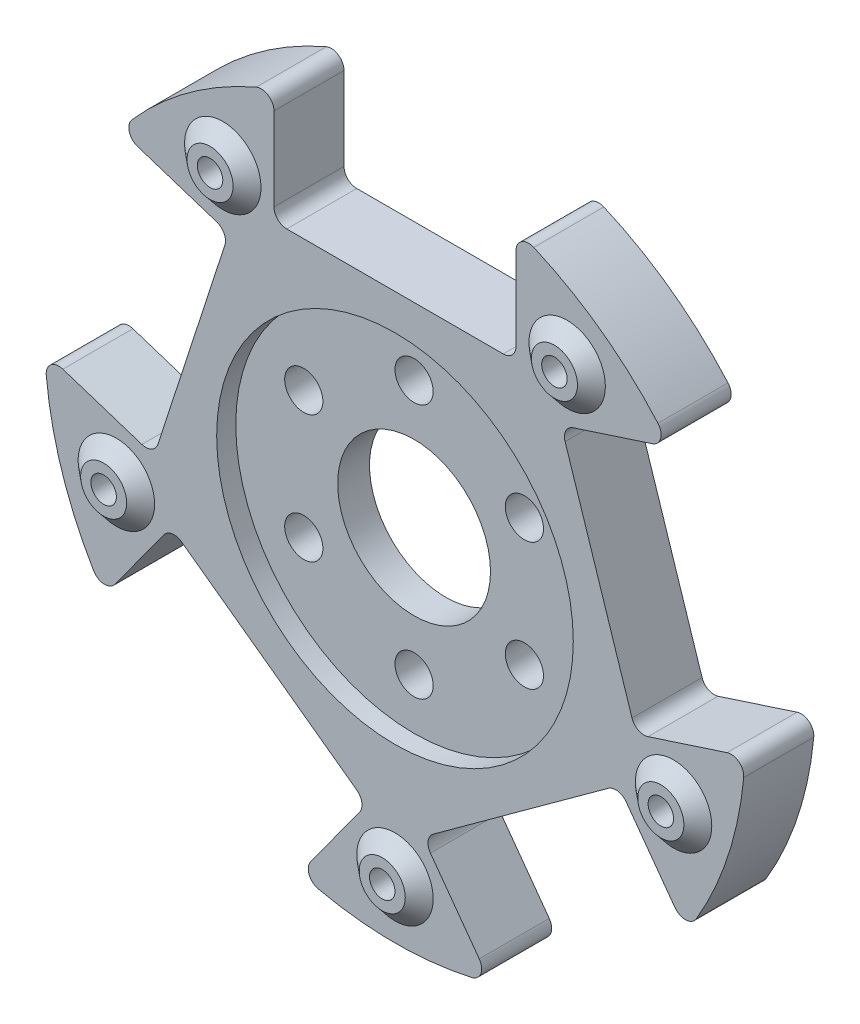
SolidWorks part; units mm, degrees
material "1060 Alloy"
ref_plane "Front Plane" through (0, 0, 0) normal (0, 0, 1) x (1, 0, 0)
ref_plane "Top Plane" through (0, 0, 0) normal (0, 1, 0) x (1, 0, 0)
ref_plane "Right Plane" through (0, 0, 0) normal (1, 0, 0) x (0, 0, -1)
sketch "Sketch2" plane through (0, 0, 0) normal (0, 0, 1) x (1, 0, 0)
  line L0 (-9.5, 25.807) -> (-9.5, 16.807)
  line L1 (-9.5, 16.807) -> (9.5, 16.807)
  line L2 (9.5, 16.807) -> (9.5, 25.807)
  line L3 (0, 0) -> (-50000, 0) construction
  line L4 (0, 0) -> (0, -50000) construction
  line L5 (21.6082, 17.0098) -> (13.0487, 14.2287)
  line L6 (18.92, -3.8414) -> (27.4796, -1.0602)
  line L7 (13.0487, 14.2287) -> (18.92, -3.8414)
  line L8 (22.8546, -15.2943) -> (17.5646, -8.0132)
  line L9 (2.1932, -19.1811) -> (7.4833, -26.4622)
  line L10 (17.5646, -8.0132) -> (2.1932, -19.1811)
  line L11 (-7.4833, -26.4622) -> (-2.1932, -19.1811)
  line L12 (-17.5646, -8.0132) -> (-22.8546, -15.2943)
  line L13 (-2.1932, -19.1811) -> (-17.5646, -8.0132)
  line L14 (-27.4796, -1.0602) -> (-18.92, -3.8414)
  line L15 (-13.0487, 14.2287) -> (-21.6082, 17.0098)
  line L16 (-18.92, -3.8414) -> (-13.0487, 14.2287)
  arc A0 (-9.5, 25.807) -> (-21.6082, 17.0098) centre (0, 0) ccw
  circle A1 centre (0, 0) radius 6
  circle A2 centre (0, 10) radius 1.5
  circle A5 centre (0, 0) radius 14
  arc A6 (21.6082, 17.0098) -> (9.5, 25.807) centre (0, 0) ccw
  arc A7 (22.8546, -15.2943) -> (27.5, 0) centre (0, 0) ccw
  arc A8 (-7.4833, -26.4622) -> (7.4833, -26.4622) centre (0, 0) ccw
  arc A9 (-27.5, 0) -> (-22.8546, -15.2943) centre (0, 0) ccw
  circle A10 centre (8.6603, 5) radius 1.5
  circle A11 centre (8.6603, -5) radius 1.5
  circle A12 centre (0, -10) radius 1.5
  circle A13 centre (-8.6603, -5) radius 1.5
  circle A14 centre (-8.6603, 5) radius 1.5
  point P12 (0, 0)
  point P39 (0, 0)
  point P47 (0, 0)
  dimension "D1" = 55
  dimension "D2" = 12
  dimension "D4" = 3
  dimension "D8" = 28
  dimension "D3" = 10
  dimension "D6" = 19
  dimension "D7" = 9
  dimension "D9" = 5
  dimension "D5" = 6
extrude "Boss-Extrude1" add sketch "Sketch2" along normal mid plane 5.5 contours L14 A9 L12 L13 L11 A8 L9 L10 L8 A7 L6 L7 L5 A6 L2 L1 L0 A0 L15 L16 A5 region at (-10.2656, 21.307, 0)
extrude "Boss-Extrude2" add sketch "Sketch2<3>" along normal mid plane 2.5 contours A5 A1 A2 region at (-13.604, 0, 0)
sketch "Sketch2<3>" plane through (0, 0, 0) normal (0, 0, 1) x (1, 0, 0) same geometry as "Sketch2"
fillet "Fillet1" radius 1 20 edges at (-18.92, -3.8414, 0) (-13.0487, 14.2287, 0) (-17.5646, -8.0132, 0) (-2.1932, -19.1811, 0) (17.5646, -8.0132, 0) (2.1932, -19.1811, 0) (18.92, -3.8414, 0) (13.0487, 14.2287, 0) (9.5, 16.807, 0) (-9.5, 16.807, 0) (-9.5, 25.807, 0) (9.5, 25.807, 0) (21.6082, 17.0098, 0) (27.4796, -1.0602, 0) (22.8546, -15.2943, 0) (7.4833, -26.4622, 0) (-7.4833, -26.4622, 0) (-22.8546, -15.2943, 0) (-27.4796, -1.0602, 0) (-21.6082, 17.0098, 0)
sketch "Sketch3" plane through (0, 0, 2.75) normal (0, 0, 1) x (1, 0, 0)
  line L0 (0, 0) -> (22.2845, 30.672) construction
  line L1 (0, 0) -> (0, 37.4243) construction
  circle A0 centre (13.5191, 18.6074) radius 3
  circle A2 centre (21.8743, -7.1074) radius 3
  circle A3 centre (0, -23) radius 3
  circle A4 centre (-21.8743, -7.1074) radius 3
  circle A5 centre (-13.5191, 18.6074) radius 3
  point P19 (0, 0)
  dimension "D2" = 6
  dimension "D1" = 23
  dimension "D3" = 36
  dimension "D4" = 5
extrude "Boss-Extrude3" add sketch "Sketch3" along normal blind 1 draft 50
sketch "Sketch4" plane through (0, 0, 3.75) normal (0, 0, 1) x (1, 0, 0)
  circle A0 centre (13.5191, 18.6074) radius 1
  circle A1 centre (21.8743, -7.1074) radius 1
  circle A2 centre (0, -23) radius 1
  circle A3 centre (-21.8743, -7.1074) radius 1
  circle A4 centre (-13.5191, 18.6074) radius 1
  point P14 (0, 0)
  dimension "D1" = 2
  dimension "D2" = 5
extrude "Cut-Extrude1" cut sketch "Sketch4" against normal blind 2
sketch "Sketch5" plane through (0, 0, -2.75) normal (0, 0, -1) x (-1, 0, 0)
  line L0 (0, 0) -> (0, -50000) construction
  line L1 (0, 0) -> (29389.2626, 40450.8497) construction
  circle A0 centre (13.5191, 18.6074) radius 3
  circle A1 centre (21.8743, -7.1074) radius 3
  circle A2 centre (0, -23) radius 3
  circle A3 centre (-21.8743, -7.1074) radius 3
  circle A4 centre (-13.5191, 18.6074) radius 3
  point P17 (0, 0)
  dimension "D2" = 6
  dimension "D1" = 23
  dimension "D3" = 36
  dimension "D4" = 5
extrude "Boss-Extrude5" add sketch "Sketch5" along normal blind 1 draft 50
sketch "Sketch6" plane through (0, 0, -3.75) normal (0, 0, -1) x (-1, 0, 0)
  circle A0 centre (13.5191, 18.6074) radius 1
  circle A1 centre (21.8743, -7.1074) radius 1
  circle A2 centre (0, -23) radius 1
  circle A3 centre (-21.8743, -7.1074) radius 1
  circle A4 centre (-13.5191, 18.6074) radius 1
  point P13 (0, 0)
  dimension "D1" = 2
  dimension "D2" = 5
extrude "Cut-Extrude2" cut sketch "Sketch6" against normal blind 1
